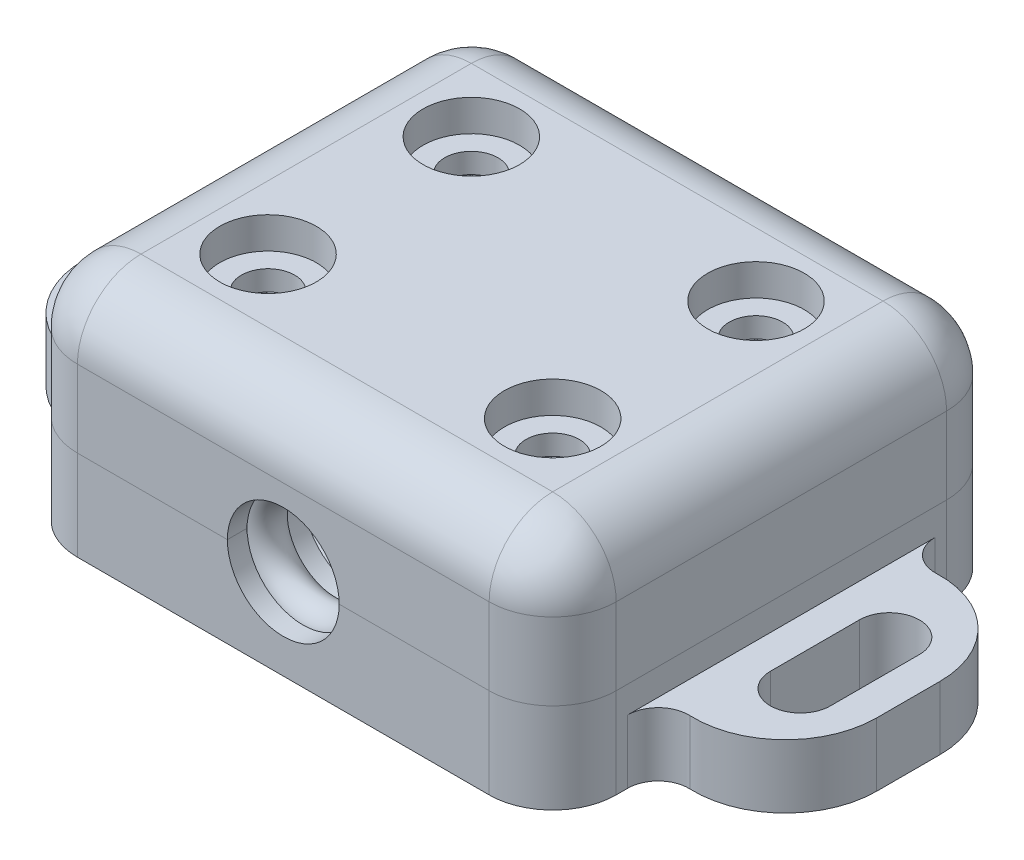
SolidWorks part; units mm, degrees
ref_plane "Front Plane" through (0, 0, 0) normal (0, 0, 1) x (1, 0, 0)
ref_plane "Top Plane" through (0, 0, 0) normal (0, 1, 0) x (1, 0, 0)
ref_plane "Right Plane" through (0, 0, 0) normal (1, 0, 0) x (0, 0, -1)
sketch "Sketch1" plane through (0, 0, 0) normal (0, 1, 0) x (1, 0, 0)
  line L5 (-9.652, -7.62) -> (9.652, -7.62)
  line L6 (-9.652, -7.62) -> (-9.652, 7.62)
  line L7 (-9.652, 7.62) -> (9.652, 7.62)
  line L8 (9.652, -7.62) -> (9.652, 7.62)
  line L9 (-9.652, -7.62) -> (9.652, 7.62) construction
  line L10 (-9.652, 7.62) -> (9.652, -7.62) construction
  line L11 (-13.462, -11.43) -> (13.462, -11.43)
  line L12 (-13.462, -11.43) -> (-13.462, 11.43)
  line L13 (-13.462, 11.43) -> (13.462, 11.43)
  line L14 (13.462, -11.43) -> (13.462, 11.43)
  line L15 (-13.462, -11.43) -> (13.462, 11.43) construction
  line L16 (-13.462, 11.43) -> (13.462, -11.43) construction
  point P0 (0, 0)
  point P6 (0, 0)
  dimension "D1" = 3.81
  dimension "D2" = 3.81
  dimension "D3" = 19.304
  dimension "D4" = 15.24
extrude "Boss-Extrude1" add sketch "Sketch1" along normal blind 4.2543
sketch "Sketch3" plane through (0, 0, 11.43) normal (0, 0, 1) x (1, 0, 0)
  line L0 (-13.462, 4.2543) -> (13.462, 4.2543) construction
  circle A0 centre (0, 4.2543) radius 2.794
  dimension "D1" = 5.588
extrude "Cut-Extrude1" cut sketch "Sketch3" against normal up to next
mirror "Mirror1" about plane through (0, 4.2543, 0) normal (0, -1, 0) of bodies 103
sketch "Sketch2" plane through (0, 0, 0) normal (0, -1, 0) x (1, 0, 0)
  line L0 (-13.462, 11.43) -> (13.462, 11.43) construction
  line L1 (13.462, -11.43) -> (-13.462, -11.43)
  line L2 (13.462, -11.43) -> (13.462, 11.43)
  line L3 (13.462, 11.43) -> (-13.462, 11.43)
  line L4 (-13.462, -11.43) -> (-13.462, 11.43)
  line L5 (13.462, -11.43) -> (-13.462, 11.43) construction
  line L6 (13.462, 11.43) -> (-13.462, -11.43) construction
  line L7 (-13.462, -11.43) -> (-13.462, 11.43) construction
  point P0 (0, 0)
extrude "Boss-Extrude2" add sketch "Sketch2" along normal blind 0.254
sketch "Sketch4" plane through (0, 4.2543, 0) normal (0, 1, 0) x (1, 0, 0)
  line L0 (2.794, -9.525) -> (10.287, -9.525)
  line L1 (2.794, -11.43) -> (2.794, -7.62) construction
  line L2 (11.557, -8.255) -> (11.557, 8.255)
  line L3 (10.287, 9.525) -> (-10.287, 9.525)
  line L4 (-11.557, 8.255) -> (-11.557, -8.255)
  line L5 (-10.287, -9.525) -> (-2.794, -9.525)
  line L6 (-2.794, -7.62) -> (-2.794, -11.43) construction
  line L7 (9.652, -7.62) -> (9.652, -9.525) construction
  line L8 (9.652, -9.525) -> (9.652, -7.62) construction
  line L9 (9.652, -7.62) -> (11.557, -7.62) construction
  line L10 (9.652, 7.62) -> (9.652, 9.525) construction
  line L11 (-9.652, 7.62) -> (-11.557, 7.62) construction
  arc A0 (10.287, -9.525) -> (11.557, -8.255) centre (10.287, -8.255) ccw
  arc A1 (-11.557, -8.255) -> (-10.287, -9.525) centre (-10.287, -8.255) ccw
  arc A2 (-10.287, 9.525) -> (-11.557, 8.255) centre (-10.287, 8.255) ccw
  arc A3 (11.557, 8.255) -> (10.287, 9.525) centre (10.287, 8.255) ccw
  dimension "D1" = 1.27
sketch "Sketch16" plane through (0, 8.5086, 0) normal (0, 1, 0) x (1, 0, 0)
  line L0 (13.462, -11.43) -> (13.462, 11.43) construction
  line L1 (-13.462, -11.43) -> (13.462, -11.43) construction
  line L2 (-13.462, 11.43) -> (-13.462, -11.43) construction
  line L3 (13.462, -11.43) -> (13.462, 11.43)
  line L4 (-13.462, -11.43) -> (13.462, -11.43)
  line L5 (-13.462, 11.43) -> (-13.462, -11.43)
  line L6 (13.462, 11.43) -> (-13.462, 11.43) construction
  line L7 (13.462, 11.43) -> (-13.462, 11.43)
extrude "Boss-Extrude7" add sketch "Sketch16" along normal blind 2.7686
ref_plane "Plane1" through (2.794, 0, 0) normal (-1, 0, 0) x (0, 0, 1)
sketch "Sketch5" plane through (2.794, 0, 0) normal (-1, 0, 0) x (0, 0, 1)
  line L0 (11.43, 4.2543) -> (7.62, 4.2543) construction
  circle A0 centre (9.525, 4.2543) radius 0.9525
  dimension "D1" = 1.905
sketch "Sketch6" plane through (0, 4.2543, 0) normal (0, 1, 0) x (1, 0, 0)
  line L0 (-11.557, 8.255) -> (-11.557, -8.255) construction
  line L5 (10.287, 9.525) -> (-10.287, 9.525) construction
  line L6 (11.557, -8.255) -> (11.557, 8.255) construction
  line L7 (-11.557, 8.255) -> (-11.557, -8.255)
  line L8 (10.287, 9.525) -> (-10.287, 9.525)
  line L9 (11.557, -8.255) -> (11.557, 8.255)
  line L10 (-10.287, -9.525) -> (10.287, -9.525)
  arc A0 (-11.557, -8.255) -> (-10.287, -9.525) centre (-10.287, -8.255) ccw construction
  arc A1 (-10.287, 9.525) -> (-11.557, 8.255) centre (-10.287, 8.255) ccw construction
  arc A2 (11.557, 8.255) -> (10.287, 9.525) centre (10.287, 8.255) ccw construction
  arc A3 (10.287, -9.525) -> (11.557, -8.255) centre (10.287, -8.255) ccw construction
  arc A4 (-11.557, -8.255) -> (-10.287, -9.525) centre (-10.287, -8.255) ccw
  arc A5 (-10.287, 9.525) -> (-11.557, 8.255) centre (-10.287, 8.255) ccw
  arc A6 (11.557, 8.255) -> (10.287, 9.525) centre (10.287, 8.255) ccw
  arc A7 (10.287, -9.525) -> (11.557, -8.255) centre (10.287, -8.255) ccw
sweep "Cut-Sweep2" cut profiles "Sketch5" path "Sketch6"
sketch "Sketch7" plane through (0, 4.2543, 0) normal (0, 1, 0) x (1, 0, 0)
  line L0 (2.794, -8.5725) -> (10.287, -8.5725) construction
  line L1 (10.287, -10.4775) -> (2.794, -10.4775) construction
  line L2 (2.794, -8.5725) -> (2.794, -7.62) construction
  circle A0 centre (3.048, -9.525) radius 0.9525
  dimension "D1" = 0.254
ref_axis "Axis1" through (0, 4.2543, 7.62) along (0, 0, 1)
revolve "Cut-Revolve1" cut sketch "Sketch7" angle 360 about axis through (0, 4.2543, 7.62) along (0, 0, 1)
sweep "Sweep1" add profiles "Sketch5<2>" path "Sketch4"
sketch "Sketch5<2>" plane through (2.794, 0, 0) normal (-1, 0, 0) x (0, 0, 1) same geometry as "Sketch5"
revolve "Revolve1" add sketch "Sketch7<2>" angle 360 about axis through (0, 4.2543, 7.62) along (0, 0, 1)
sketch "Sketch7<2>" plane through (0, 4.2543, 0) normal (0, 1, 0) x (1, 0, 0) same geometry as "Sketch7"
sketch "Sketch17" plane through (0, 8.5086, 0) normal (0, -1, 0) x (1, 0, 0)
  line L4 (9.652, 7.62) -> (-9.652, 7.62)
  line L5 (-9.652, 7.62) -> (-9.652, -7.62)
  line L6 (-9.652, -7.62) -> (9.652, -7.62)
  line L7 (9.652, -7.62) -> (9.652, 7.62)
  line L8 (9.652, 7.62) -> (-9.652, 7.62)
  line L9 (-9.652, 7.62) -> (-9.652, -7.62)
  line L10 (-9.652, -7.62) -> (9.652, -7.62)
  line L11 (9.652, -7.62) -> (9.652, 7.62)
  dimension "D1" = 0
extrude "Cut-Extrude6" cut sketch "Sketch17" against normal blind 1.5875
sketch "Sketch13" plane through (0, 10.0961, 0) normal (0, -1, 0) x (1, 0, 0)
  line L1 (9.652, -7.62) -> (-9.652, -7.62)
  line L2 (9.652, -7.62) -> (9.652, 7.62)
  line L3 (9.652, 7.62) -> (-9.652, 7.62)
  line L4 (-9.652, -7.62) -> (-9.652, 7.62)
  line L5 (9.652, -7.62) -> (-9.652, 7.62) construction
  line L6 (9.652, 7.62) -> (-9.652, -7.62) construction
  point P0 (0, 0)
extrude "Boss-Extrude5" add sketch "Sketch13" along normal blind 0.4
ref_plane "Top of PCB" through (0, 8.6961, 0) normal (0, -1, 0) x (-1, 0, 0)
sketch "Sketch10" plane through (0, 9.6961, 0) normal (0, -1, 0) x (1, 0, 0)
  line L1 (9.652, -7.62) -> (-9.652, -7.62) construction
  line L2 (0, 0) -> (0, -50000) construction
  line L3 (0, 0) -> (-50000, 0) construction
  line L8 (7.112, -2.032) -> (9.652, -2.032)
  line L9 (4.064, -5.08) -> (4.064, -7.62)
  line L10 (4.064, -7.62) -> (9.652, -7.62)
  line L11 (9.652, -7.62) -> (9.652, -2.032)
  line L12 (-9.652, -7.62) -> (-9.652, -2.032)
  line L13 (-4.064, -7.62) -> (-9.652, -7.62)
  line L14 (-4.064, -5.08) -> (-4.064, -7.62)
  line L15 (-7.112, -2.032) -> (-9.652, -2.032)
  line L16 (-7.112, 2.032) -> (-9.652, 2.032)
  line L17 (-4.064, 5.08) -> (-4.064, 7.62)
  line L18 (-4.064, 7.62) -> (-9.652, 7.62)
  line L19 (-9.652, 7.62) -> (-9.652, 2.032)
  line L20 (9.652, 7.62) -> (9.652, 2.032)
  line L21 (4.064, 7.62) -> (9.652, 7.62)
  line L22 (4.064, 5.08) -> (4.064, 7.62)
  line L23 (7.112, 2.032) -> (9.652, 2.032)
  line L24 (9.652, 7.62) -> (9.652, -7.62) construction
  arc A0 (7.112, -2.032) -> (4.064, -5.08) centre (7.112, -5.08) ccw
  arc A1 (-7.112, -2.032) -> (-4.064, -5.08) centre (-7.112, -5.08) cw
  arc A2 (-7.112, 2.032) -> (-4.064, 5.08) centre (-7.112, 5.08) ccw
  arc A3 (7.112, 2.032) -> (4.064, 5.08) centre (7.112, 5.08) cw
  dimension "D3" = 3.048
  dimension "D1" = 2.54
  dimension "D2" = 2.54
extrude "Boss-Extrude4" add sketch "Sketch10" along normal up to surface (1 mm away) up to plane "Top of PCB"
ref_plane "Bottom of PCB" through (0, 7.0961, 0) normal (0, -1, 0) x (-1, 0, 0)
sketch "Sketch11" plane through (0, 7.0961, 0) normal (0, -1, 0) x (1, 0, 0)
  line L0 (0, 0) -> (0, 50000) construction
  line L1 (0, 0) -> (50000, 0) construction
  circle A0 centre (7.112, 5.08) radius 1.3335
  circle A2 centre (7.112, -5.08) radius 1.3335
  circle A3 centre (-7.112, 5.08) radius 1.3335
  circle A4 centre (-7.112, -5.08) radius 1.3335
  arc A5 (4.064, 5.08) -> (7.112, 2.032) centre (7.112, 5.08) ccw construction
  dimension "D1" = 2.667
extrude "Cut-Extrude2" cut sketch "Sketch11" against normal through all
sketch "Sketch12" plane through (0, 11.2772, 0) normal (0, 1, 0) x (1, 0, 0)
  line L0 (0, 0) -> (0, -50000) construction
  line L1 (0, 0) -> (-50000, 0) construction
  circle A0 centre (-7.112, -5.08) radius 2.413
  circle A2 centre (-7.112, 5.08) radius 2.413
  circle A3 centre (7.112, -5.08) radius 2.413
  circle A4 centre (7.112, 5.08) radius 2.413
  dimension "D1" = 4.826
  dimension "D2" = 5.08
  dimension "D3" = 7.112
extrude "Cut-Extrude3" cut sketch "Sketch12" against normal blind 1.5748
fillet "Fillet2" radius 3.175 8 edges at (13.462, 7.7657, -11.43) (-13.462, 7.7657, -11.43) (-13.462, 7.7657, 11.43) (13.462, 7.7657, 11.43) (13.462, 11.2772, 0) (0, 11.2772, -11.43) (0, 11.2772, 11.43) (-13.462, 11.2772, 0)
fillet "Fillet3" radius 0.508 12 edges at (4.064, 9.6961, 6.35) (8.382, 9.6961, 2.032) (8.382, 9.6961, -2.032) (4.064, 9.6961, -6.35) (-8.382, 9.6961, 2.032) (-4.064, 9.6961, 6.35) (-8.382, 9.6961, -2.032) (-4.9567, 9.6961, -2.9247) (4.9567, 9.6961, 2.9247) (4.9567, 9.6961, -2.9247) (-4.9567, 9.6961, 2.9247) (-4.064, 9.6961, -6.35)
sketch "Sketch18" plane through (0, 0, 0) normal (0, 1, 0) x (1, 0, 0)
  line L4 (-9.652, 7.62) -> (-9.652, -7.62)
  line L5 (-9.652, -7.62) -> (9.652, -7.62)
  line L6 (9.652, -7.62) -> (9.652, 7.62)
  line L7 (9.652, 7.62) -> (-9.652, 7.62)
  line L8 (-9.652, 7.62) -> (-9.652, -7.62)
  line L9 (-9.652, -7.62) -> (9.652, -7.62)
  line L10 (9.652, -7.62) -> (9.652, 7.62)
  line L11 (9.652, 7.62) -> (-9.652, 7.62)
  dimension "D1" = 0
extrude "Boss-Extrude8" add sketch "Sketch18" along normal blind 1.27
sketch "Sketch19" plane through (0, 1.27, 0) normal (0, 1, 0) x (1, 0, 0)
  line L0 (9.652, 7.62) -> (-9.652, 7.62) construction
  line L1 (9.652, -7.62) -> (4.572, -7.62)
  line L2 (9.652, -7.62) -> (9.652, 7.62)
  line L3 (9.652, 7.62) -> (4.572, 7.62)
  line L4 (4.572, -7.62) -> (4.572, 7.62)
  line L5 (0, -0.0214) -> (0, -50000.0214) construction
  line L6 (-4.572, -7.62) -> (-4.572, 7.62)
  line L7 (-9.652, 7.62) -> (-4.572, 7.62)
  line L8 (-9.652, -7.62) -> (-9.652, 7.62)
  line L9 (-9.652, -7.62) -> (-4.572, -7.62)
  dimension "D1" = 5.08
extrude "Boss-Extrude9" add sketch "Sketch19" along normal up to surface (5.8261 mm away) up to plane "Bottom of PCB"
extrude "Cut-Extrude5" cut sketch "Sketch11<2>" along normal blind 4.572 draft 4
sketch "Sketch11<2>" plane through (0, 7.0961, 0) normal (0, -1, 0) x (1, 0, 0) same geometry as "Sketch11"
fillet "Fillet5" radius 3.175 4 edges at (-13.462, 2.0002, -11.43) (-13.462, 2.0002, 11.43) (13.462, 2.0002, -11.43) (13.462, 2.0002, 11.43)
sketch "Sketch14" plane through (0, -0.254, 0) normal (0, -1, 0) x (1, 0, 0)
  line L0 (13.462, 7.6782) -> (13.462, -7.6782)
  line L1 (13.462, -8.255) -> (13.462, 8.255) construction
  line L3 (0, 0) -> (50000, 0) construction
  line L4 (19.812, -1.5875) -> (19.812, 1.5875)
  line L5 (16.637, 2.2225) -> (16.637, -2.2225) construction
  line L6 (18.137, 2.2225) -> (18.137, -2.2225)
  line L7 (15.137, 2.2225) -> (15.137, -2.2225)
  line L8 (16.637, -1.0957) -> (13.462, -1.0957) construction
  line L9 (13.462, -1.0957) -> (16.637, -1.0957) construction
  line L10 (16.637, -1.0957) -> (19.812, -1.0957) construction
  line L11 (0, 0) -> (0, 50000) construction
  line L12 (-16.637, 2.2225) -> (-16.637, -2.2225) construction
  line L13 (-18.137, 2.2225) -> (-18.137, -2.2225)
  line L14 (-15.137, 2.2225) -> (-15.137, -2.2225)
  line L15 (-16.637, -1.0957) -> (-19.812, -1.0957) construction
  line L16 (-13.462, -1.0957) -> (-16.637, -1.0957) construction
  line L17 (-16.637, -1.0957) -> (-13.462, -1.0957) construction
  line L18 (-19.812, -1.5875) -> (-19.812, 1.5875)
  line L19 (-13.462, 7.6782) -> (-13.462, -7.6782)
  arc A0 (13.462, -7.6782) -> (15.0495, -6.1555) centre (14.986, -7.6782) cw
  arc A3 (15.0495, -6.1555) -> (19.812, -1.5875) centre (15.24, -1.5875) ccw
  arc A4 (15.0495, 6.1555) -> (19.812, 1.5875) centre (15.24, 1.5875) cw
  arc A5 (13.462, 7.6782) -> (15.0495, 6.1555) centre (14.986, 7.6782) ccw
  arc A6 (18.137, 2.2225) -> (15.137, 2.2225) centre (16.637, 2.2225) ccw
  arc A7 (15.137, -2.2225) -> (18.137, -2.2225) centre (16.637, -2.2225) ccw
  arc A8 (-18.137, 2.2225) -> (-15.137, 2.2225) centre (-16.637, 2.2225) cw
  arc A9 (-15.137, -2.2225) -> (-18.137, -2.2225) centre (-16.637, -2.2225) cw
  arc A10 (-13.462, 7.6782) -> (-15.0495, 6.1555) centre (-14.986, 7.6782) cw
  arc A11 (-15.0495, 6.1555) -> (-19.812, 1.5875) centre (-15.24, 1.5875) ccw
  arc A12 (-15.0495, -6.1555) -> (-19.812, -1.5875) centre (-15.24, -1.5875) cw
  arc A13 (-13.462, -7.6782) -> (-15.0495, -6.1555) centre (-14.986, -7.6782) ccw
  point P7 (13.462, 0)
  point P17 (19.812, 0)
  point P19 (16.637, 0)
  point P31 (-16.637, 0)
  point P49 (-19.812, 0)
  point P50 (-13.462, 0)
  dimension "D1" = 1.524
  dimension "D2" = 4.572
  dimension "D6" = 1.5
  dimension "D3" = 6.35
  dimension "D4" = 3.175
  dimension "D5" = 4.445
extrude "Boss-Extrude6" add sketch "Sketch14" against normal blind 3.175
